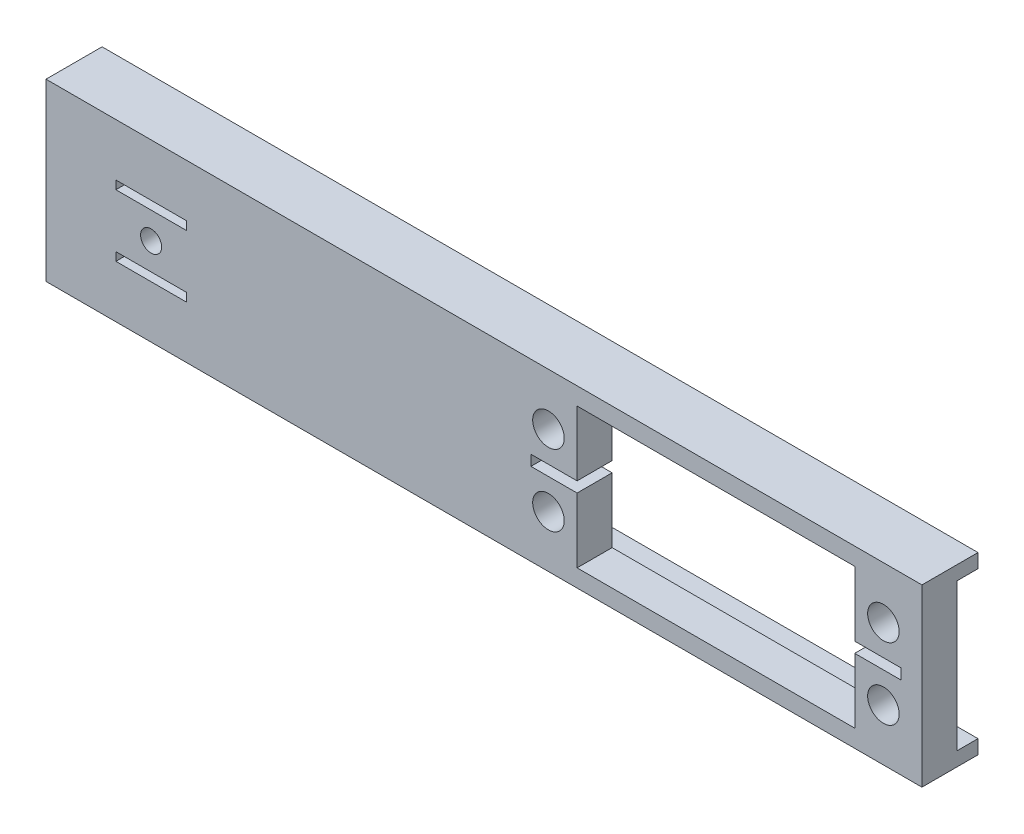
SolidWorks part; units mm, degrees
ref_plane "Front Plane" through (0, 0, 0) normal (0, 0, 1) x (1, 0, 0)
ref_plane "Top Plane" through (0, 0, 0) normal (0, 1, 0) x (1, 0, 0)
ref_plane "Right Plane" through (0, 0, 0) normal (1, 0, 0) x (0, 0, -1)
sketch "Sketch1" plane through (0, 0, 0) normal (0, 0, 1) x (1, 0, 0)
  line L1 (-62.5, -12.5) -> (62.5, -12.5)
  line L2 (-62.5, -12.5) -> (-62.5, 12.5)
  line L3 (-62.5, 12.5) -> (62.5, 12.5)
  line L4 (62.5, -12.5) -> (62.5, 12.5)
  line L5 (-62.5, -12.5) -> (62.5, 12.5) construction
  line L6 (-62.5, 12.5) -> (62.5, -12.5) construction
  line L7 (-42.4708, -5.0292) -> (-52.5292, -5.0292)
  line L8 (-42.4708, -5.0292) -> (-42.4708, 5.0292)
  line L9 (-42.4708, 5.0292) -> (-52.5292, 5.0292)
  line L10 (-52.5292, -5.0292) -> (-52.5292, 5.0292)
  line L11 (-42.4708, -5.0292) -> (-52.5292, 5.0292) construction
  line L12 (-42.4708, 5.0292) -> (-52.5292, -5.0292) construction
  line L13 (-52.5292, -3.8227) -> (-42.4708, -3.8227)
  line L14 (-52.5292, -3.8227) -> (-52.5292, 3.8227)
  line L15 (-52.5292, 3.8227) -> (-42.4708, 3.8227)
  line L16 (-42.4708, -3.8227) -> (-42.4708, 3.8227)
  line L17 (-52.5292, -3.8227) -> (-42.4708, 3.8227) construction
  line L18 (-52.5292, 3.8227) -> (-42.4708, -3.8227) construction
  line L23 (13.288, 0.75) -> (6.7, 0.75)
  line L24 (13.288, 0.75) -> (13.288, -0.75)
  line L25 (9.2, -5.1) -> (57, -5.1) construction
  line L26 (59.5, -10) -> (6.7, -10)
  line L27 (59.5, -10) -> (59.5, 10)
  line L28 (59.5, 10) -> (6.7, 10)
  line L29 (6.7, -10) -> (6.7, 10)
  line L30 (59.5, -10) -> (6.7, 10) construction
  line L31 (59.5, 10) -> (6.7, -10) construction
  line L32 (13.288, -0.75) -> (6.7, -0.75)
  line L33 (13.288, -10) -> (52.912, -10)
  line L34 (13.288, -10) -> (13.288, 10)
  line L35 (13.288, 10) -> (52.912, 10)
  line L36 (52.912, -10) -> (52.912, 10)
  line L37 (13.288, -10) -> (52.912, 10) construction
  line L38 (13.288, 10) -> (52.912, -10) construction
  line L39 (6.7, 0.75) -> (6.7, -0.75)
  line L40 (52.912, 0.75) -> (59.5, 0.75)
  line L41 (52.912, 0.75) -> (52.912, -0.75)
  line L42 (52.912, -0.75) -> (59.5, -0.75)
  line L43 (59.5, 0.75) -> (59.5, -0.75)
  circle A3 centre (-47.5, 0) radius 1.5
  circle A8 centre (9.2, 5.1) radius 2.25
  circle A9 centre (9.2, -5.1) radius 2.25
  circle A10 centre (57, -5.1) radius 2.25
  circle A11 centre (57, 5.1) radius 2.25
  point P0 (0, 0)
  point P6 (-47.5, 0)
  point P11 (-47.5, 0)
  point P18 (33.1, 0)
  point P28 (6.7, 0)
  point P29 (13.288, 0)
  point P46 (33.1, -5.1)
  point P49 (62.5, 0)
  point P50 (33.1, 0)
  point P52 (43.1, 0)
  dimension "D6" = 3
  dimension "D16" = 4.5
  dimension "D2" = 25
  dimension "D1" = 10.0584
  dimension "D3" = 1.2065
  dimension "D4" = 15
  dimension "D5" = 125
  dimension "D14" = 52.8
  dimension "D15" = 20
  dimension "D17" = 10.2
  dimension "D18" = 4.9
  dimension "D19" = 33.9
  dimension "D20" = 13.9
  dimension "D21" = 3
  dimension "D22" = 39.624
  dimension "D7" = 1.5
extrude "Boss-Extrude1" add sketch "Sketch1" along normal blind 5 contours L1 L4 L3 L2 L7 L10 L9 L8 L26 L29 L28 L27 | L15 L10 L13 L8 A3 | L36 L40 L27 L28 A11 | L42 L36 L26 L27 A10 | L26 L34 L32 L29 A9 | L23 L34 L28 L29 A8 region at (-15.3204, 0, 0) region at (-47.5, -3.6964, 0) region at (9.994, 0.8636, 0) region at (13.1744, -5.375, 0) region at (56.206, 9.8864, 0) region at (53.0256, -5.375, 0)
chamfer "Chamfer1" [suppressed] distance 0.5 angle 45
sketch "Sketch3" plane through (0, 12.5, 0) normal (0, 1, 0) x (1, 0, 0)
  line L0 (62.5, -5) -> (62.5, 0) construction
  line L1 (-62.5, -5) -> (62.5, -5)
  line L2 (-62.5, -5) -> (-62.5, 3)
  line L3 (-62.5, 3) -> (62.5, 3)
  line L4 (62.5, -5) -> (62.5, 3)
  dimension "D1" = 8
extrude "Boss-Extrude2" add sketch "Sketch3" against normal blind 2
extrude "Boss-Extrude3" add sketch "Sketch3<2>" along normal blind 2 from surface starting at face at (0, -12.5, 2.5)
sketch "Sketch3<2>" plane through (0, 12.5, 0) normal (0, 1, 0) x (1, 0, 0) same geometry as "Sketch3"
equation "\"Length\" = 125"
equation "\"D5@Sketch1\"=\"Length\""
